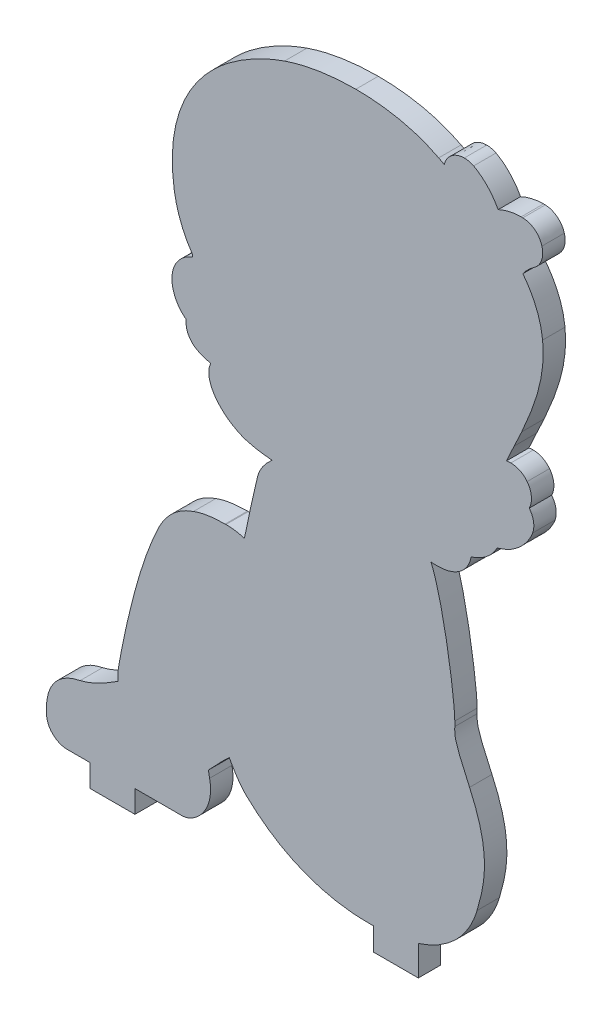
SolidWorks part; units mm, degrees
ref_plane "Front Plane" through (0, 0, 0) normal (0, 0, 1) x (1, 0, 0)
ref_plane "Top Plane" through (0, 0, 0) normal (0, 1, 0) x (1, 0, 0)
ref_plane "Right Plane" through (0, 0, 0) normal (1, 0, 0) x (0, 0, -1)
sketch "Model" plane through (0, 0, 0) normal (0, 0, 1) x (1, 0, 0)
  line L0 (256.3814, -381.177) -> (256.2929, -381.1776)
  line L1 (240.1006, -409.3273) -> (251.7731, -409.3304)
  line L2 (254.6988, -404.584) -> (254.5702, -403.9198)
  line L3 (278.795, -337.9595) -> (278.22, -337.657)
  spline S0 degree 3 poles (269.7165, -335.8018) (267.1337, -335.8017) (264.532, -336.2142) (262.3905, -336.9631) knots 1 1 1 1 2 2 2 2
  spline S1 degree 3 poles (262.3905, -336.9631) (260.4021, -337.6584) (257.5253, -338.9821) (255.1123, -341.3398) knots 2 2 2 2 3 3 3 3
  spline S2 degree 3 poles (255.1123, -341.3398) (252.0577, -344.3244) (250.604, -348.2192) (250.9085, -352.6033) knots 3 3 3 3 4 4 4 4
  spline S3 degree 3 poles (250.9085, -352.6033) (250.9812, -353.6468) (251.1679, -356.3265) (252.9161, -358.8373) knots 4 4 4 4 5 5 5 5
  spline S4 degree 3 poles (252.9161, -358.8373) (252.9275, -358.9385) (252.9379, -359.0301) (252.9468, -359.1116) knots 5 5 5 5 6 6 6 6
  spline S5 degree 3 poles (252.9468, -359.1116) (252.436, -359.3029) (251.9731, -359.6121) (251.6156, -360.0137) knots 6 6 6 6 7 7 7 7
  spline S6 degree 3 poles (251.6156, -360.0137) (250.7968, -360.9346) (250.6058, -362.2136) (251.1039, -363.4359) knots 7 7 7 7 8 8 8 8
  spline S7 degree 3 poles (251.1039, -363.4359) (251.37, -364.0891) (251.7827, -364.6141) (252.2981, -364.981) knots 8 8 8 8 9 9 9 9
  spline S8 degree 3 poles (252.2981, -364.981) (252.2686, -365.2057) (252.2749, -365.4356) (252.319, -365.6613) knots 9 9 9 9 10 10 10 10
  spline S9 degree 3 poles (252.319, -365.6613) (252.4315, -366.2362) (252.781, -366.7429) (253.2778, -367.0522) knots 10 10 10 10 11 11 11 11
  spline S10 degree 3 poles (253.2778, -367.0522) (253.4512, -367.1603) (253.9636, -367.4451) (254.8135, -367.641) knots 11 11 11 11 12 12 12 12
  spline S11 degree 3 poles (254.8135, -367.641) (254.6381, -368.0158) (254.5696, -368.4433) (254.6371, -368.8704) knots 12 12 12 12 13 13 13 13
  spline S12 degree 3 poles (254.6371, -368.8704) (254.926, -370.6955) (256.8951, -372.1992) (258.6012, -372.6875) knots 13 13 13 13 14 14 14 14
  spline S13 degree 3 poles (258.6012, -372.6875) (259.3725, -372.9077) (260.2614, -373.0294) (261.1075, -373.0935) knots 14 14 14 14 15 15 15 15
  spline S14 degree 3 poles (261.1075, -373.0935) (260.4192, -373.706) (259.8272, -374.4523) (259.6227, -375.3042) knots 15 15 15 15 16 16 16 16
  spline S15 degree 3 poles (259.6227, -375.3042) (259.1727, -377.1789) (258.6683, -379.4919) (258.2739, -381.4614) knots 16 16 16 16 17 17 17 17
  spline S16 degree 3 poles (258.2739, -381.4614) (257.6735, -381.2741) (257.0371, -381.177) (256.3814, -381.177) knots 17 17 17 17 18 18 18 18
  spline S17 degree 3 poles (256.2929, -381.1776) (254.7295, -381.203) (253.9458, -381.3753) (253.0444, -381.6846) knots 19 19 19 19 20 20 20 20
  spline S18 degree 3 poles (253.0444, -381.6846) (251.484, -382.2209) (250.3369, -383.2343) (249.5367, -384.7829) knots 20 20 20 20 21 21 21 21
  spline S19 degree 3 poles (249.5367, -384.7829) (248.6996, -386.4022) (247.7418, -389.0824) (246.9748, -391.9523) knots 21 21 21 21 22 22 22 22
  spline S20 degree 3 poles (246.9748, -391.9523) (246.0085, -395.5666) (245.4844, -398.5869) (245.3887, -399.1613) knots 22 22 22 22 23 23 23 23
  spline S21 degree 3 poles (245.3887, -399.1613) (245.3249, -399.4785) (245.2436, -400.0398) (245.2966, -400.6707) knots 23 23 23 23 24 24 24 24
  spline S22 degree 3 poles (245.2966, -400.6707) (244.0183, -401.5046) (242.529, -402.3028) (241.4141, -402.5372) knots 24 24 24 24 25 25 25 25
  spline S23 degree 3 poles (241.4141, -402.5372) (238.3291, -403.1852) (237.8318, -405.4998) (237.958, -407.3273) knots 25 25 25 25 26 26 26 26
  spline S24 degree 3 poles (237.958, -407.3273) (238.0358, -408.4491) (238.9769, -409.3273) (240.1006, -409.3273) knots 26 26 26 26 27 27 27 27
  spline S25 degree 3 poles (251.7731, -409.3304) (252.1091, -409.3304) (252.4446, -409.2503) (252.7438, -409.0988) knots 28 28 28 28 29 29 29 29
  spline S26 degree 3 poles (252.7438, -409.0988) (253.6998, -408.6166) (255.1906, -407.1214) (254.6988, -404.584) knots 29 29 29 29 30 30 30 30
  spline S27 degree 3 poles (254.5702, -403.9198) (254.8408, -403.6512) (255.1369, -403.338) (255.4785, -402.9687) knots 31 31 31 31 32 32 32 32
  spline S28 degree 3 poles (255.4785, -402.9687) (255.7309, -402.696) (255.9856, -402.4208) (256.1477, -402.2669) knots 32 32 32 32 33 33 33 33
  spline S29 degree 3 poles (256.1477, -402.2669) (256.2854, -402.1359) (256.452, -401.9827) (256.6332, -401.8162) knots 33 33 33 33 34 34 34 34
  spline S30 degree 3 poles (256.6332, -401.8162) (256.6611, -401.7904) (256.6888, -401.7649) (256.7163, -401.7396) knots 34 34 34 34 35 35 35 35
  spline S31 degree 3 poles (256.7163, -401.7396) (257.3184, -402.8574) (257.8896, -403.6798) (258.4232, -404.1958) knots 35 35 35 35 36 36 36 36
  spline S32 degree 3 poles (258.4232, -404.1958) (261.8748, -407.5324) (266.2244, -409.2959) (271.0019, -409.2959) knots 36 36 36 36 37 37 37 37
  spline S33 degree 3 poles (271.0019, -409.2959) (276.9174, -409.2959) (280.8794, -406.9236) (282.1583, -402.616) knots 37 37 37 37 38 38 38 38
  spline S34 degree 3 poles (282.1583, -402.616) (283.0359, -399.6579) (283.5841, -396.8207) (281.3926, -392.0433) knots 38 38 38 38 39 39 39 39
  spline S35 degree 3 poles (281.3926, -392.0433) (279.8506, -388.6822) (279.8563, -388.3339) (279.8714, -387.4031) knots 39 39 39 39 40 40 40 40
  spline S36 degree 3 poles (279.8714, -387.4031) (279.874, -387.2505) (279.8765, -387.0865) (279.8765, -386.9059) knots 40 40 40 40 41 41 41 41
  spline S37 degree 3 poles (279.8765, -386.9059) (279.8765, -385.0916) (278.7666, -377.1451) (277.4355, -373.9856) knots 41 41 41 41 42 42 42 42
  spline S38 degree 3 poles (277.4355, -373.9856) (277.5455, -373.997) (277.6459, -374.0044) (277.7354, -374.009) knots 42 42 42 42 43 43 43 43
  spline S39 degree 3 poles (277.7354, -374.009) (277.8432, -374.0144) (277.9458, -374.0168) (278.044, -374.0168) knots 43 43 43 43 44 44 44 44
  spline S40 degree 3 poles (278.044, -374.0168) (280.4935, -374.0168) (281.3902, -372.4576) (281.5338, -371.5363) knots 44 44 44 44 45 45 45 45
  spline S41 degree 3 poles (281.5338, -371.5363) (281.5367, -371.5171) (281.5393, -371.498) (281.5416, -371.4788) knots 45 45 45 45 46 46 46 46
  spline S42 degree 3 poles (281.5416, -371.4788) (282.7911, -371.1034) (283.6582, -370.3075) (284.0786, -369.5989) knots 46 46 46 46 47 47 47 47
  spline S43 degree 3 poles (284.0786, -369.5989) (284.1274, -369.5172) (284.1701, -369.4327) (284.2069, -369.3462) knots 47 47 47 47 48 48 48 48
  spline S44 degree 3 poles (284.2069, -369.3462) (284.2694, -369.3289) (284.3314, -369.311) (284.3928, -369.2925) knots 48 48 48 48 49 49 49 49
  spline S45 degree 3 poles (284.3928, -369.2925) (286.9841, -368.5116) (287.7876, -366.4226) (287.8707, -366.187) knots 49 49 49 49 50 50 50 50
  spline S46 degree 3 poles (287.8707, -366.187) (288.1159, -365.4966) (287.9819, -364.7237) (287.5211, -364.1529) knots 50 50 50 50 51 51 51 51
  spline S47 degree 3 poles (287.5211, -364.1529) (287.8868, -363.4323) (287.8072, -362.5438) (287.3046, -361.8963) knots 51 51 51 51 52 52 52 52
  spline S48 degree 3 poles (287.3046, -361.8963) (286.9072, -361.3841) (286.2817, -361.0782) (285.6315, -361.0782) knots 52 52 52 52 53 53 53 53
  spline S49 degree 3 poles (285.6315, -361.0782) (285.4784, -361.0782) (285.3262, -361.0946) (285.1772, -361.1273) knots 53 53 53 53 54 54 54 54
  spline S50 degree 3 poles (285.1772, -361.1273) (285.3926, -360.5889) (285.7317, -359.8954) (285.9675, -359.4134) knots 54 54 54 54 55 55 55 55
  spline S51 degree 3 poles (285.9675, -359.4134) (286.2352, -358.8657) (286.5041, -358.3154) (286.749, -357.7542) knots 55 55 55 55 56 56 56 56
  spline S52 degree 3 poles (286.749, -357.7542) (287.8121, -355.3196) (289.2682, -351.9847) (288.8927, -348.5219) knots 56 56 56 56 57 57 57 57
  spline S53 degree 3 poles (288.8927, -348.5219) (288.6487, -346.2729) (287.6232, -344.5996) (286.8601, -343.6366) knots 57 57 57 57 58 58 58 58
  spline S54 degree 3 poles (286.8601, -343.6366) (287.0911, -343.2978) (287.5195, -342.8496) (287.9783, -342.5328) knots 58 58 58 58 59 59 59 59
  spline S55 degree 3 poles (287.9783, -342.5328) (288.7388, -342.0097) (289.0742, -341.0778) (288.8232, -340.2003) knots 60 60 60 60 61 61 61 61
  spline S56 degree 3 poles (288.8232, -340.2003) (288.5703, -339.3155) (287.7823, -338.699) (286.8623, -338.6669) knots 61 61 61 61 62 62 62 62
  spline S57 degree 3 poles (286.8623, -338.6669) (286.8008, -338.6649) (286.7452, -338.6641) (286.6901, -338.6641) knots 62 62 62 62 63 63 63 63
  spline S58 degree 3 poles (286.6901, -338.6641) (285.8956, -338.664) (285.0958, -338.8501) (284.3268, -339.2053) knots 63 63 63 63 64 64 64 64
  spline S59 degree 3 poles (284.3268, -339.2053) (283.3995, -337.439) (282.0182, -336.6868) (281.8081, -336.5803) knots 64 64 64 64 65 65 65 65
  spline S60 degree 3 poles (281.8081, -336.5803) (281.5106, -336.43) (281.1807, -336.3514) (280.8511, -336.3514) knots 65 65 65 65 66 66 66 66
  spline S61 degree 3 poles (280.8511, -336.3514) (280.0765, -336.3513) (279.3643, -336.7735) (278.9927, -337.4532) knots 66 66 66 66 67 67 67 67
  spline S62 degree 3 poles (278.9927, -337.4532) (278.9037, -337.6173) (278.8382, -337.7873) (278.795, -337.9595) knots 67 67 67 67 68 68 68 68
  spline S63 degree 3 poles (278.22, -337.657) (275.3058, -336.1238) (271.9873, -335.8018) (269.7165, -335.8018) knots 69 69 69 69 70 70 70 70
base flange "Base-Flange1" sketch "Model" thickness 2.3 reverse thickness direction no parameters "D1"=0.7366
sketch "Sketch6" plane through (0, 0, 0) normal (0, 0, 1) x (1, 0, 0)
  line L0 (240.1006, -409.3273) -> (251.7731, -409.3304) construction
  line L1 (242.4317, -409.3279) -> (247.0317, -409.3279)
  line L2 (242.4317, -409.3279) -> (242.4317, -411.6279)
  line L3 (242.4317, -411.6279) -> (247.0317, -411.6279)
  line L4 (247.0317, -409.3279) -> (247.0317, -411.6279)
  line L6 (271.5317, -411.6279) -> (276.1317, -411.6279)
  line L7 (271.5317, -411.6279) -> (271.5317, -408.3119)
  line L8 (271.5317, -408.3119) -> (276.1317, -408.3119)
  line L9 (276.1317, -411.6279) -> (276.1317, -408.3119)
  dimension "D1" = 2.3
  dimension "D2" = 4.6
  dimension "D3" = 4.6
  dimension "D4" = 24.5
base flange "Tab1" sketch "Sketch6" thickness 2.3 reverse thickness direction no parameters "D1"=0.7366
sketch "Bend-Lines1" [suppressed] plane through (0, 0, 0) normal (0, 1, 0) x (1, 0, 0)
sketch "Bounding-Box1" [suppressed] plane through (0, 0, 0) normal (0, 1, 0) x (1, 0, 0)
sheet metal parameters "Sheet-Metal1" thickness 2.3 parameters "D1"=0.7366
flat pattern "Flat-Pattern1" [suppressed]
sketch "Bend-Lines2" plane through (0, 0, 0) normal (0, 1, 0) x (1, 0, 0)
sketch3d "Bounding-Box2" [suppressed]
  line L0 (-6.7122, -79.3117, 0) -> (-18.448, -1.8897, 0) construction
  line L1 (36.1808, -72.8099, 0) -> (24.4451, 4.6121, 0) construction
  line L2 (-6.7122, -79.3117, 0) -> (36.1808, -72.8099, 0) construction
  line L3 (-18.448, -1.8897, 0) -> (24.4451, 4.6121, 0) construction
sheet metal parameters "Sheet-Metal2" thickness 2.3 parameters "D1"=0.7366
flat pattern "Flat-Pattern2"
sketch "Bend-Lines3" plane through (0, 0, 0) normal (0, 1, 0) x (1, 0, 0)
sketch3d "Bounding-Box3" [suppressed]
  line L0 (4.5429, -83.69, 0) -> (22.8698, -3.7528, 0) construction
  line L1 (-36.7542, -74.2219, 0) -> (-18.4274, 5.7153, 0) construction
  line L2 (4.5429, -83.69, 0) -> (-36.7542, -74.2219, 0) construction
  line L3 (22.8698, -3.7528, 0) -> (-18.4274, 5.7153, 0) construction
